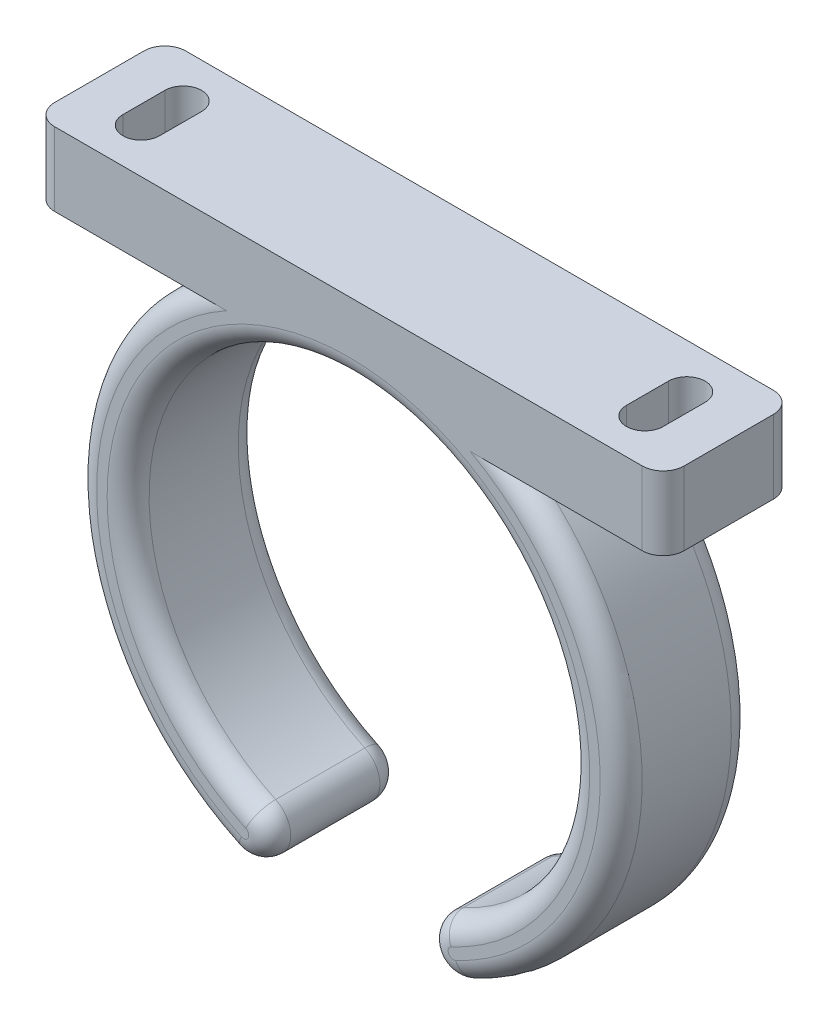
SolidWorks part; units mm, degrees
ref_plane "Alzado" through (0, 0, 0) normal (0, 0, 1) x (1, 0, 0)
ref_plane "Planta" through (0, 0, 0) normal (0, 1, 0) x (1, 0, 0)
ref_plane "Vista lateral" through (0, 0, 0) normal (1, 0, 0) x (0, 0, -1)
sketch "Croquis1" plane through (0, 0, 0) normal (0, 0, 1) x (1, 0, 0)
  line L0 (0, 21) -> (0, -20) construction
  line L1 (-30, 28) -> (30, 21) construction
  line L2 (-30, 28) -> (30, 28)
  line L3 (-30, 28) -> (-30, 21)
  line L4 (-30, 21) -> (-15.3297, 21)
  line L5 (30, 28) -> (30, 21)
  line L6 (15.3297, 21) -> (30, 21)
  arc A0 (8.9362, -19.0038) -> (-8.9362, -19.0038) centre (0, 0) ccw
  arc A1 (11.0638, -23.5285) -> (15.3297, 21) centre (0, 0) ccw
  arc A2 (-11.0638, -23.5285) -> (-8.9362, -19.0038) centre (-10, -21.2662) ccw
  arc A3 (11.0638, -23.5285) -> (8.9362, -19.0038) centre (10, -21.2662) cw
  circle A4 centre (0, 0) radius 26 construction
  circle A5 centre (0, 0) radius 21 construction
  arc A6 (-15.3297, 21) -> (-11.0638, -23.5285) centre (0, 0) ccw
  point P17 (0, 24.5)
  dimension "D1" = 42
  dimension "D3" = 10
  dimension "D4" = 7
  dimension "D5" = 60
  dimension "D2" = 5
extrude "Saliente-Extruir1" add sketch "Croquis1" along normal blind 12.5
fillet "Redondeo1" radius 2 14 edges at (25.8815, -2.4795, 0) (7.7376, -22.33, 0) (0, 21, 0) (-7.7376, -22.33, 0) (-25.8815, -2.4795, 12.5) (-7.7376, -22.33, 12.5) (25.8815, -2.4795, 12.5) (7.7376, -22.33, 12.5) (-25.8815, -2.4795, 0) (0, 21, 12.5) (-30, 24.5, 0) (-30, 24.5, 12.5) (30, 24.5, 0) (30, 24.5, 12.5)
sketch "Croquis3" plane through (0, 21, 0) normal (0, -1, 0) x (1, 0, 0)
  line L0 (-24, 8.25) -> (-24, 4.25) construction
  line L1 (-22.25, 8.25) -> (-22.25, 4.25)
  line L2 (-25.75, 8.25) -> (-25.75, 4.25)
  line L3 (24, 8.25) -> (24, 4.25) construction
  line L4 (25.75, 8.25) -> (25.75, 4.25)
  line L5 (22.25, 8.25) -> (22.25, 4.25)
  line L6 (-30, 6.25) -> (30, 6.25) construction
  line L7 (-30, 10.5) -> (-30, 2) construction
  line L8 (30, 10.5) -> (30, 2) construction
  arc A0 (-22.25, 8.25) -> (-25.75, 8.25) centre (-24, 8.25) ccw
  arc A1 (-25.75, 4.25) -> (-22.25, 4.25) centre (-24, 4.25) ccw
  arc A2 (25.75, 8.25) -> (22.25, 8.25) centre (24, 8.25) ccw
  arc A3 (22.25, 4.25) -> (25.75, 4.25) centre (24, 4.25) ccw
  point P2 (-24, 6.25)
  point P9 (24, 6.25)
  dimension "D3" = 1.75
  dimension "D1" = 6
  dimension "D2" = 6
  dimension "D4" = 4
extrude "Cortar-Extruir1" cut sketch "Croquis3" against normal up to next
